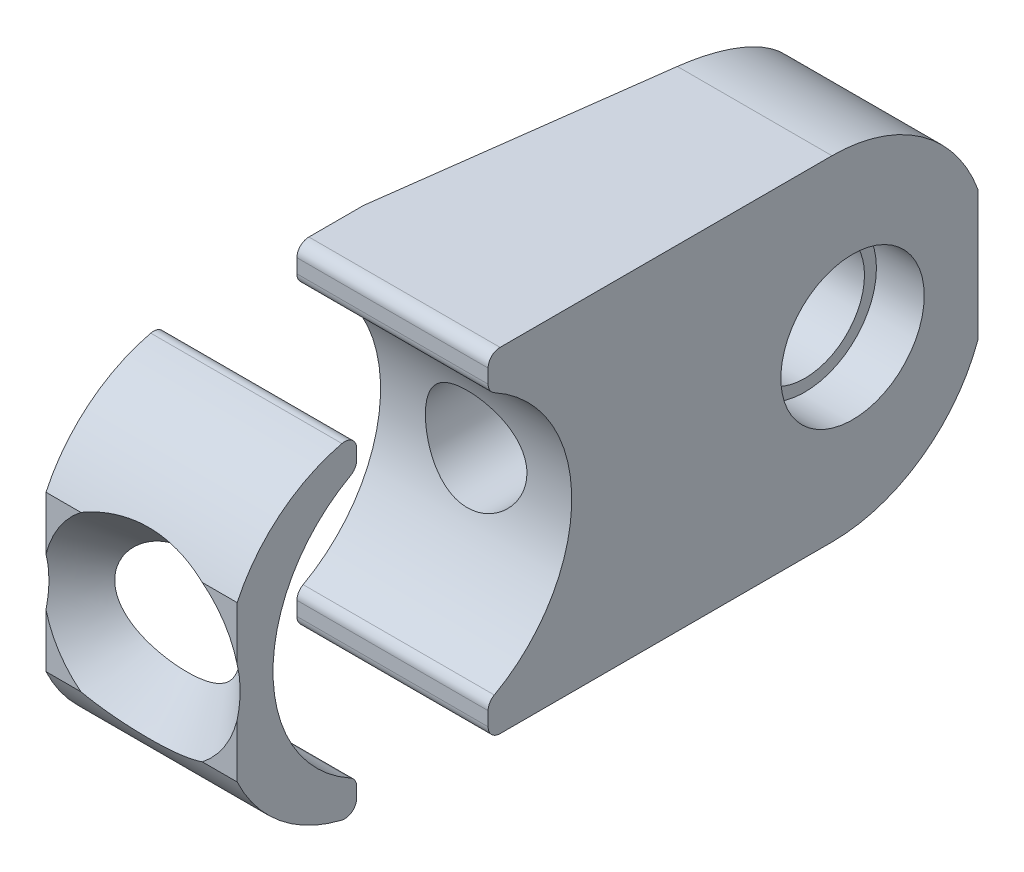
SolidWorks part; units mm, degrees
material "1060 Сплав"
ref_plane "Спереди" through (0, 0, 0) normal (0, 0, 1) x (1, 0, 0)
ref_plane "Сверху" through (0, 0, 0) normal (0, 1, 0) x (1, 0, 0)
ref_plane "Справа" through (0, 0, 0) normal (1, 0, 0) x (0, 0, -1)
sketch "Эскиз1" plane through (0, 0, 0) normal (1, 0, 0) x (0, 0, -1)
  line L1 (32, 14) -> (-32, 14)
  line L2 (32, 14) -> (32, -14)
  line L3 (32, -14) -> (-32, -14)
  line L4 (-32, 14) -> (-32, -14)
  line L5 (32, 14) -> (-32, -14) construction
  line L6 (32, -14) -> (-32, 14) construction
  point P0 (0, 0)
  dimension "D1" = 28
  dimension "D2" = 64
extrude "Бобышка-Вытянуть1" add sketch "Эскиз1" along normal blind 16
fillet "Скругление1" radius 13 4 edges at (8, 14, -32) (8, -14, -32) (8, 14, 32) (8, -14, 32)
sketch "Эскиз2" plane through (0, 0, 0) normal (-1, 0, 0) x (0, 0, 1)
  line L0 (30.7792, 6.5) -> (30.7792, -6.5)
  line L1 (30.7792, 6.5) -> (37.7974, 6.5)
  line L2 (37.7974, 6.5) -> (37.7974, -6.5)
  line L3 (37.7974, -6.5) -> (30.7792, -6.5)
  line L4 (-31.2208, 5.4331) -> (-31.2208, -5.4331)
  line L5 (-36.3818, -5.4331) -> (-36.3818, 5.4331)
  line L6 (-36.3818, 5.4331) -> (-31.2208, 5.4331)
  line L7 (-36.3818, -5.4331) -> (-31.2208, -5.4331)
  arc A0 (32, 1) -> (19, 14) centre (19, 1) ccw construction
  arc A1 (19, -14) -> (32, -1) centre (19, -1) ccw construction
  circle A2 centre (15.2792, 0) radius 12.5
  arc A3 (-19, 14) -> (-32, 1) centre (-19, 1) ccw construction
  arc A4 (-32, -1) -> (-19, -14) centre (-19, -1) ccw construction
  dimension "D2" = 25
  dimension "D4" = 62
  dimension "D1" = 13
  dimension "D3" = 15.5
extrude "Вырез-Вытянуть1" cut sketch "Эскиз2" against normal through all
sketch "Эскиз3" plane through (0, 0, 0) normal (-1, 0, 0) x (0, 0, 1)
  line L0 (-31.2208, -5.4331) -> (-31.2208, 5.4331) construction
  circle A0 centre (-20.7208, 0) radius 8.5
  dimension "D1" = 17
  dimension "D2" = 10.5
extrude "Вырез-Вытянуть2" cut sketch "Эскиз3" against normal blind 5
sketch "Эскиз4" plane through (0, 0, -31.2208) normal (0, 0, -1) x (-1, 0, 0)
  line L0 (0, -2) -> (-7, -20)
  line L1 (-7, -20) -> (5, -20)
  line L2 (5, -20) -> (5, -2)
  line L3 (5, -2) -> (0, -2)
  dimension "D1" = 0
  dimension "D2" = 2
  dimension "D3" = 7
  dimension "D4" = 20
  dimension "D5" = 5
extrude "Вырез-Вытянуть3" cut sketch "Эскиз4" against normal through all draft 7
mirror "Зеркальное отражение1" about plane through (0, 0, 0) normal (0, 1, 0) of "Вырез-Вытянуть3"
sketch "Эскиз5" plane through (0, -14, 0) normal (0, -1, 0) x (-1, 0, 0)
  line L0 (-1.3233, 23.9031) -> (-1.0729, 33.8121)
  line L1 (-1.0729, 33.8121) -> (2.3992, 33.7243)
  line L2 (2.3992, 33.7243) -> (2.3992, 23.8091)
  line L3 (2.3992, 23.8091) -> (-1.3233, 23.9031)
  ellipse E0 centre (2.1611, 20.7208) end of major axis (0.8487, 29.2061) minor radius 3.2724 (0, 28.7311) -> (0, 16.088) ccw construction
extrude "Вырез-Вытянуть4" cut sketch "Эскиз5" against normal through all
sketch "Эскиз6" plane through (5, 0, 0) normal (-1, 0, 0) x (0, 0, 1)
  circle A0 centre (-20.7208, 0) radius 5
  circle A1 centre (-20.7208, 0) radius 8.5 construction
  dimension "D1" = 10
extrude "Вырез-Вытянуть5" cut sketch "Эскиз6" against normal through all
sketch "Эскиз7" plane through (16, 0, 0) normal (1, 0, 0) x (0, 0, -1)
  circle A0 centre (20.7208, 0) radius 6
extrude "Вырез-Вытянуть6" cut sketch "Эскиз7" against normal blind 4
sketch "Эскиз8" plane through (0, 0, 0) normal (-1, 0, 0) x (0, 0, 1)
  line L0 (9.7792, 15.9511) -> (9.7792, -17.0467)
  line L1 (9.7792, -17.0467) -> (20.7792, -17.0467)
  line L2 (20.7792, -17.0467) -> (20.7792, 15.9511)
  line L3 (20.7792, 15.9511) -> (9.7792, 15.9511)
  line L5 (30.7792, 6.5) -> (30.7792, -6.5) construction
  dimension "D1" = 11
  dimension "D2" = 10
extrude "Вырез-Вытянуть7" cut sketch "Эскиз8" against normal through all
sketch "Эскиз9" plane through (0, 0, 30.7792) normal (0, 0, 1) x (1, 0, 0)
  line L0 (16, 6.5) -> (16, -6.5) construction
  circle A0 centre (8, 0) radius 4.25
  dimension "D1" = 8.5
  dimension "D2" = 8
extrude "Вырез-Вытянуть8" cut sketch "Эскиз9" against normal blind 40
fillet "Скругление2" radius 1 4 edges at (8, -14, 9.7792) (8, -11.225, 9.7792) (8, 11.225, 9.7792) (8, 14, 9.7792)
fillet "Скругление3" radius 1 4 edges at (8, 13.8777, 20.7792) (8, 11.225, 20.7792) (8, -13.8777, 20.7792) (8, -11.225, 20.7792)
chamfer "Фаска1" distance 4 angle 45 1 edges at (12.25, 0, 30.7792)
